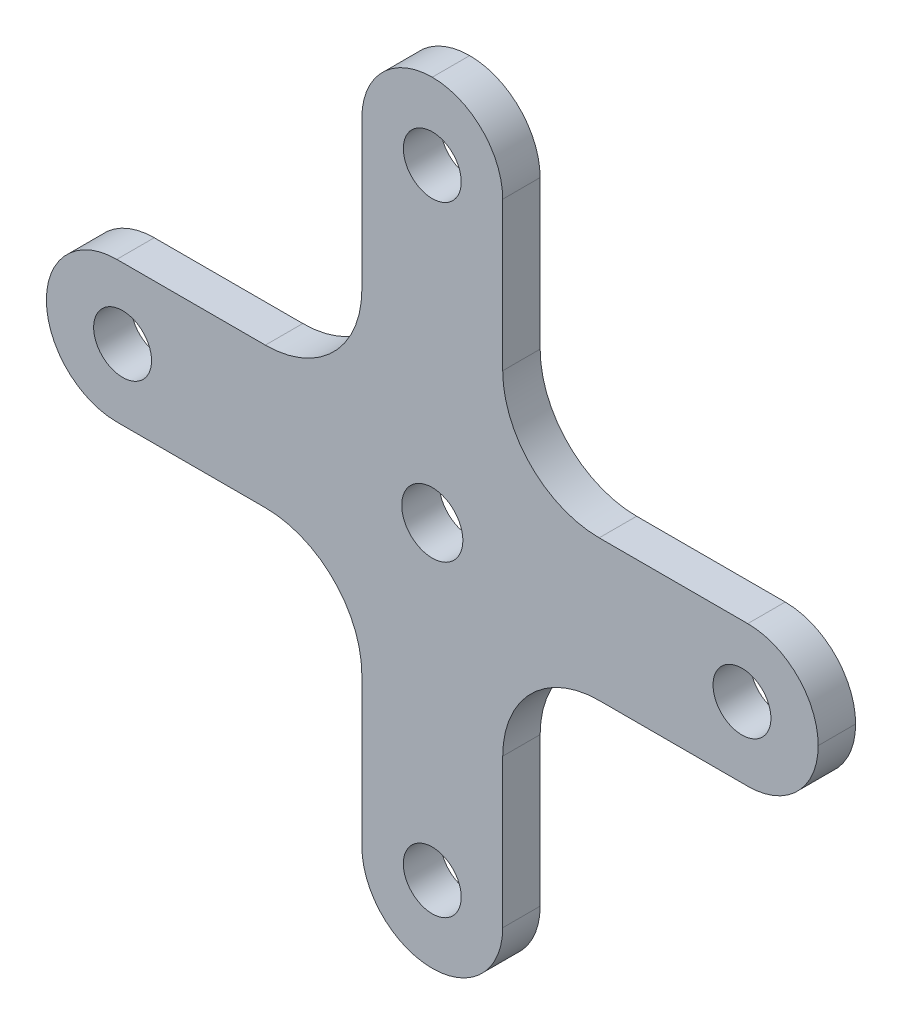
SolidWorks part; units mm, degrees
ref_plane "Front Plane" through (0, 0, 0) normal (0, 0, 1) x (1, 0, 0)
ref_plane "Top Plane" through (0, 0, 0) normal (0, 1, 0) x (1, 0, 0)
ref_plane "Right Plane" through (0, 0, 0) normal (1, 0, 0) x (0, 0, -1)
sketch "Sketch2" plane through (0, 0, 0) normal (0, 0, 1) x (1, 0, 0)
  line L0 (20, 0) -> (-20, 0) construction
  line L1 (-20, -20) -> (20, -20)
  line L2 (-20, -20) -> (-20, 20)
  line L3 (-20, 20) -> (20, 20)
  line L4 (20, -20) -> (20, 20)
  line L5 (-20, -20) -> (20, 20) construction
  line L6 (-20, 20) -> (20, -20) construction
  line L7 (-20, 20) -> (-3.65, 20)
  line L8 (-20, 20) -> (-20, 3.65)
  line L9 (-20, 3.65) -> (-3.65, 3.65)
  line L10 (-3.65, 20) -> (-3.65, 3.65)
  line L11 (20, 20) -> (3.65, 20)
  line L12 (20, 20) -> (20, 3.65)
  line L13 (20, 3.65) -> (3.65, 3.65)
  line L14 (3.65, 20) -> (3.65, 3.65)
  line L15 (20, -20) -> (20, -3.65)
  line L16 (20, -20) -> (3.65, -20)
  line L17 (3.65, -20) -> (3.65, -3.65)
  line L18 (20, -3.65) -> (3.65, -3.65)
  line L19 (-20, -20) -> (-3.65, -20)
  line L20 (-20, -20) -> (-20, -3.65)
  line L21 (-20, -3.65) -> (-3.65, -3.65)
  line L22 (-3.65, -20) -> (-3.65, -3.65)
  circle A0 centre (0, 16.05) radius 1.5
  circle A1 centre (16.05, 0) radius 1.5
  circle A2 centre (0, -16.05) radius 1.5
  circle A3 centre (-16.05, 0) radius 1.5
  point P0 (0, 0)
  point P12 (0, 0)
  point P27 (0, 0)
  point P30 (0, 0)
  point P33 (0, 0)
  point P36 (0, 0)
  point P39 (0, 0)
  dimension "D4" = 3
  dimension "D5" = 3.95
  dimension "D1" = 40
  dimension "D2" = 3.65
  dimension "D3" = 4
  dimension "D6" = 4
extrude "Boss-Extrude1" add sketch "Sketch2" along normal mid plane 1.94 contours L22 L1 L17 L18 L4 L13 L14 L3 L10 L9 L2 L21 A3 A2 A1 A0 region at (0, 0, 0)
fillet "Fillet1" radius 3.65 8 edges at (20, 3.65, 0) (20, -3.65, 0) (3.65, -20, 0) (-3.65, -20, 0) (-20, -3.65, 0) (-20, 3.65, 0) (3.65, 20, 0) (-3.65, 20, 0)
fillet "Fillet2" radius 5 4 edges at (-3.65, -3.65, 0) (3.65, -3.65, 0) (3.65, 3.65, 0) (-3.65, 3.65, 0)
sketch "Sketch3" plane through (0, 0, 0.97) normal (0, 0, 1) x (1, 0, 0)
  circle A0 centre (0, 0) radius 1.585
  dimension "D1" = 3.17
extrude "Cut-Extrude1" cut sketch "Sketch3" along direction (0, 0, 1) on the side against the normal through all
sketch "Sketch4" plane through (0, 0, 0.97) normal (0, 0, 1) x (1, 0, 0)
  point P0 (0, 16.05)
  point P1 (16.05, 0)
  point P3 (-16.05, 0)
  point P5 (0, -16.05)
